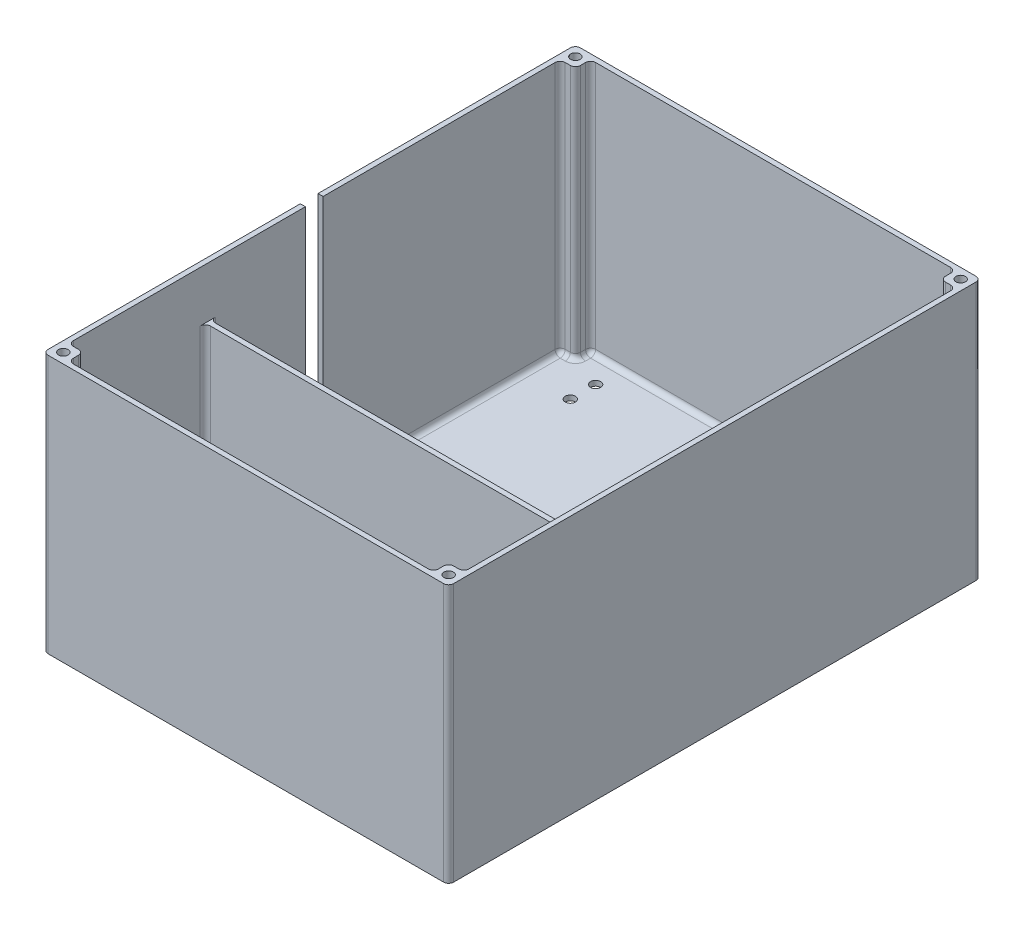
SolidWorks part; units mm, degrees
ref_plane "Front Plane" through (0, 0, 0) normal (0, 0, 1) x (1, 0, 0)
ref_plane "Top Plane" through (0, 0, 0) normal (0, 1, 0) x (1, 0, 0)
ref_plane "Right Plane" through (0, 0, 0) normal (1, 0, 0) x (0, 0, -1)
sketch "Sketch1" plane through (0, 0, 0) normal (0, 1, 0) x (1, 0, 0)
  line L1 (0, 0) -> (160, 0)
  line L2 (0, 0) -> (0, 210)
  line L3 (0, 210) -> (160, 210)
  line L4 (160, 0) -> (160, 210)
  dimension "D1" = 160
  dimension "D2" = 210
extrude "Boss-Extrude3" add sketch "Sketch1" along normal blind 2
sketch "Sketch3" plane through (0, 2, 0) normal (0, 1, 0) x (1, 0, 0)
  line L5 (0, 210) -> (160, 210)
  line L6 (0, 210) -> (0, 0)
  line L7 (0, 0) -> (160, 0)
  line L8 (2, 208) -> (2, 2)
  line L9 (2, 2) -> (158, 2)
  line L10 (158, 2) -> (158, 208)
  line L11 (158, 208) -> (2, 208)
  line L12 (2, 202) -> (2, 8)
  line L13 (8, 2) -> (152, 2)
  line L14 (158, 8) -> (158, 202)
  line L15 (152, 208) -> (8, 208)
  line L16 (160, 210) -> (160, 0)
  line L19 (2, 202) -> (8, 202)
  line L20 (8, 208) -> (8, 202)
  line L23 (158, 202) -> (152, 202)
  line L24 (152, 208) -> (152, 202)
  line L27 (2, 8) -> (8, 8)
  line L28 (8, 2) -> (8, 8)
  line L31 (158, 8) -> (152, 8)
  line L32 (152, 2) -> (152, 8)
  dimension "D2" = 6
  dimension "D1" = 2
extrude "Boss-Extrude4" add sketch "Sketch3" along normal blind 100
ref_plane "Plane1" through (80, 0, 0) normal (1, 0, 0) x (0, 0, -1)
ref_plane "Plane2" through (0, 0, -105) normal (0, 0, 1) x (1, 0, 0)
fillet "Fillet1" radius 2 16 edges at (160, 51, -210) (160, 51, 0) (0, 51, 0) (0, 51, -210) (2, 52, -8) (8, 52, -8) (8, 52, -2) (152, 52, -2) (152, 52, -8) (158, 52, -8) (158, 52, -202) (152, 52, -202) (152, 52, -208) (8, 52, -202) (8, 52, -208) (2, 52, -202)
sketch "Sketch4" plane through (0, 102, 0) normal (0, 1, 0) x (1, 0, 0)
  line L0 (4, 206) -> (4, 210) construction
  line L1 (158, 210) -> (2, 210) construction
  line L2 (4, 206) -> (0, 206) construction
  line L3 (0, 208) -> (0, 2) construction
  line L4 (80, -56.1) -> (80, 56.1) construction
  line L5 (156, 206) -> (160, 206) construction
  line L6 (156, 206) -> (156, 210) construction
  line L7 (-56.1, 105) -> (56.1, 105) construction
  line L8 (156, 4) -> (156, 0) construction
  line L9 (156, 4) -> (160, 4) construction
  line L10 (4, 4) -> (0, 4) construction
  line L11 (4, 4) -> (4, 0) construction
  circle A0 centre (4, 206) radius 1.875
  circle A1 centre (156, 206) radius 1.875
  circle A2 centre (156, 4) radius 1.875
  circle A3 centre (4, 4) radius 1.875
  dimension "D3" = 3.75
  dimension "D1" = 4
  dimension "D2" = 4
extrude "Cut-Extrude1" cut sketch "Sketch4" against normal blind 10
sketch "Sketch5" plane through (0, 2, 0) normal (0, 1, 0) x (1, 0, 0)
  line L0 (20, 198) -> (140, 198) construction
  line L1 (140, 198) -> (140, 188) construction
  line L2 (140, 188) -> (20, 188) construction
  line L3 (20, 188) -> (20, 198) construction
  line L4 (-56.1, 105) -> (56.1, 105) construction
  line L5 (20, 198) -> (2, 198) construction
  line L6 (2, 200) -> (2, 10) construction
  line L7 (140, 198) -> (158, 198) construction
  line L8 (158, 10) -> (158, 200) construction
  circle A0 centre (20, 198) radius 2
  circle A1 centre (140, 198) radius 2
  circle A2 centre (140, 188) radius 2
  circle A3 centre (20, 188) radius 2
  circle A4 centre (20, 22) radius 2
  circle A5 centre (140, 22) radius 2
  circle A6 centre (140, 12) radius 2
  circle A7 centre (20, 12) radius 2
  dimension "D5" = 4
  dimension "D1" = 120
  dimension "D2" = 10
  dimension "D4" = 10
extrude "Cut-Extrude2" cut sketch "Sketch5" against normal blind 10
sketch "Sketch6" plane through (0, 2, 0) normal (0, 1, 0) x (1, 0, 0)
  line L0 (2, 200) -> (2, 10) construction
  line L1 (2, 64) -> (158, 64)
  line L2 (2, 64) -> (2, 62)
  line L3 (2, 62) -> (158, 62)
  line L4 (158, 64) -> (158, 62)
  line L5 (158, 10) -> (158, 200) construction
  line L6 (10, 2) -> (150, 2) construction
  dimension "D1" = 2
  dimension "D2" = 60
extrude "Boss-Extrude5" add sketch "Sketch6" along normal blind 80
fillet "Fillet2" radius 2 32 edges at (158, 2, -36) (157.4142, 2, -8.5858) (155, 2, -8) (152.5858, 2, -7.4142) (152, 2, -5) (151.4142, 2, -2.5858) (80, 2, -2) (8.5858, 2, -2.5858) (8, 2, -5) (7.4142, 2, -7.4142) (5, 2, -8) (2.5858, 2, -8.5858) (158, 2, -132) (157.4142, 2, -201.4142) (155, 2, -202) (152.5858, 2, -202.5858) (152, 2, -205) (151.4142, 2, -207.4142) (80, 2, -208) (8.5858, 2, -207.4142) (8, 2, -205) (7.4142, 2, -202.5858) (5, 2, -202) (2.5858, 2, -201.4142) (2, 2, -36) (2, 42, -62) (80, 2, -62) (158, 42, -62) (158, 42, -64) (2, 42, -64) (80, 2, -64) (2, 2, -132)
sketch "Sketch7" plane through (0, 0, 0) normal (-1, 0, 0) x (0, 0, 1)
  line L0 (-105, -56.1) -> (-105, 56.1) construction
  line L1 (-108.5, 102) -> (-101.5, 102)
  line L2 (-108.5, 102) -> (-108.5, 29.746)
  line L4 (-101.5, 102) -> (-101.5, 29.746)
  line L5 (-208, 102) -> (-2, 102) construction
  arc A0 (-108.5, 29.746) -> (-101.5, 29.746) centre (-105, 22) ccw
  point P4 (-105, 102)
  dimension "D3" = 17
  dimension "D1" = 72.254
extrude "Cut-Extrude3" cut sketch "Sketch7" against normal blind 10 contours L2 A0 L4 L1
